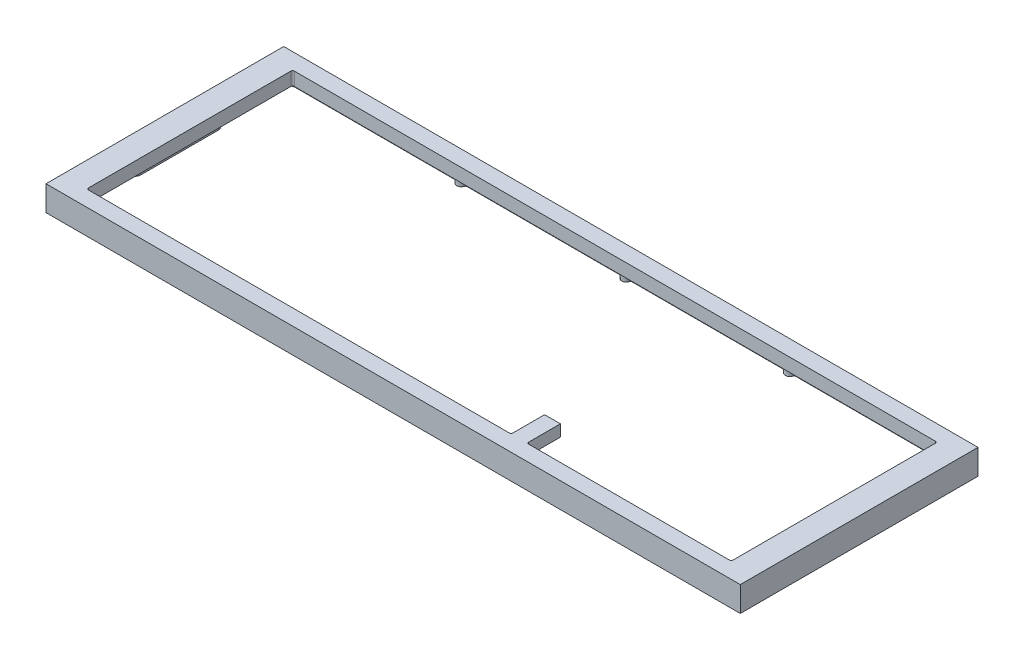
SolidWorks part; units mm, degrees
ref_plane "Front Plane" through (0, 0, 0) normal (0, 0, 1) x (1, 0, 0)
ref_plane "Top Plane" through (0, 0, 0) normal (0, 1, 0) x (1, 0, 0)
ref_plane "Right Plane" through (0, 0, 0) normal (1, 0, 0) x (0, 0, -1)
sketch "Sketch1" plane through (0, 0, 0) normal (0, 1, 0) x (1, 0, 0)
  line L1 (0, 0) -> (390.8, 0)
  line L2 (0, 0) -> (0, -133.8)
  line L3 (0, -133.8) -> (390.8, -133.8)
  line L4 (390.8, 0) -> (390.8, -133.8)
  dimension "D1" = 390.8
  dimension "D2" = 133.8
extrude "Boss-Extrude1" add sketch "Sketch1" along normal blind 14.1
sketch "Sketch2" plane through (0, 14.1, 0) normal (0, 1, 0) x (1, 0, 0)
  line L0 (390.8, 0) -> (0, 0) construction
  line L1 (14, -9) -> (376.8, -9)
  line L2 (14, -9) -> (14, -124.9)
  line L3 (14, -124.9) -> (376.8, -124.9)
  line L4 (376.8, -9) -> (376.8, -124.9)
  line L5 (0, -133.8) -> (390.8, -133.8) construction
  line L6 (0, 0) -> (0, -133.8) construction
  line L7 (390.8, -133.8) -> (390.8, 0) construction
  line L8 (390.8, -133.8) -> (390.8, 0) construction
  line L9 (261.8, -124.9) -> (252.9, -124.9)
  line L10 (261.8, -124.9) -> (261.8, -106.05)
  line L11 (261.8, -106.05) -> (252.9, -106.05)
  line L12 (252.9, -124.9) -> (252.9, -106.05)
  line L13 (0, -133.8) -> (390.8, -133.8) construction
  dimension "D1" = 9
  dimension "D2" = 8.9
  dimension "D3" = 14
  dimension "D4" = 14
  dimension "D5" = 129
  dimension "D6" = 137.9
  dimension "D7" = 27.75
extrude "Cut-Extrude1" cut sketch "Sketch2" against normal through all contours L3 L12 L11 L10 L4 L1 L2 region at (195.1518, 14.1, 66.7556)
sketch "Sketch3" plane through (0, 0, 0) normal (0, -1, 0) x (1, 0, 0)
  line L0 (390.8, 0) -> (0, 0) construction
  line L1 (385.5, 2.6) -> (5.3, 2.6)
  line L2 (385.5, 2.6) -> (385.5, 131.2)
  line L3 (385.5, 131.2) -> (5.3, 131.2)
  line L4 (5.3, 2.6) -> (5.3, 131.2)
  line L5 (390.8, 133.8) -> (390.8, 0) construction
  point P4 (195.4, 2.6)
  point P7 (195.4, 0)
  point P8 (385.5, 66.9)
  point P11 (390.8, 66.9)
  dimension "D1" = 380.2
  dimension "D2" = 128.6
extrude "Cut-Extrude2" cut sketch "Sketch3" against normal blind 6.6 contours L2 L1 L4 L3
sketch "Sketch5" plane through (0, 6.6, 0) normal (0, -1, 0) x (1, 0, 0)
  line L0 (290, 128.2) -> (285, 128.2)
  line L1 (290, 128.2) -> (290, 131.2)
  line L2 (290, 131.2) -> (285, 131.2)
  line L3 (285, 128.2) -> (285, 131.2)
  line L4 (105, 128.2) -> (100, 128.2)
  line L5 (105, 128.2) -> (105, 131.2)
  line L6 (105, 131.2) -> (100, 131.2)
  line L7 (100, 128.2) -> (100, 131.2)
  line L8 (8.3, 45) -> (8.3, 88.8)
  line L9 (382.5, 45) -> (382.5, 88.8)
  line L10 (0, 133.8) -> (390.8, 133.8) construction
  line L11 (5.3, 2.6) -> (5.3, 131.2) construction
  line L12 (390.8, 0) -> (0, 0) construction
  line L13 (385.5, 2.6) -> (385.5, 131.2) construction
  line L15 (385.5, 131.2) -> (5.3, 131.2) construction
  line L16 (385.5, 131.2) -> (5.3, 131.2) construction
  line L17 (385.5, 2.6) -> (5.3, 2.6) construction
  line L18 (5.3, 2.6) -> (5.3, 131.2) construction
  circle A0 centre (102.5, 128.2) radius 2.5
  circle A1 centre (287.5, 128.2) radius 2.5
  circle A2 centre (102.5, 2.6) radius 2.5
  circle A3 centre (195.4, 2.6) radius 2.5
  circle A4 centre (287.5, 2.6) radius 2.5
  circle A5 centre (385.5, 45) radius 3
  circle A6 centre (385.5, 88.8) radius 3
  circle A7 centre (5.3, 45) radius 3
  circle A8 centre (5.3, 88.8) radius 3
  point P26 (0, 0)
  point P35 (0, 0)
  point P38 (0, 0)
  line M9 (5.3, 131.2) -> (5.3, 2.6)
  line M10 (5.3, 2.6) -> (385.5, 2.6)
  line M11 (385.5, 2.6) -> (385.5, 131.2)
  dimension "D1" = 5
  dimension "D5" = 6
  dimension "D2" = 185
  dimension "D3" = 92.9
  dimension "D4" = 185
  dimension "D6" = 45
  dimension "D7" = 97.2
  dimension "D8" = 3
  dimension "D9" = 97.2
  dimension "D10" = 45
  dimension "D11" = 45
extrude "Boss-Extrude2" add sketch "Sketch5" along normal up to surface (6.6 mm away) contours A6 L9 A5 M11 | A5 M11 | A6 M11 | A4 M10 | A3 M10 | A2 M10 | A7 M9 | A8 A7 L8 M9 | A8 M9 | A0 | L7 L6 L5 L4 | L3 L2 L1 L0 | A1 region at (6.8273, 6.6, 66.9) region at (6.5732, 6.6, 45) region at (384.2268, 6.6, 45) region at (287.5, 6.6, 3.661) region at (195.4, 6.6, 3.661) region at (102.5, 6.6, 3.661) region at (6.5732, 6.6, 88.8) region at (383.9727, 6.6, 66.9) region at (384.2268, 6.6, 88.8) up to face at (195.4, 0, 66.9)
sketch "Sketch6" plane through (0, 6.6, 0) normal (0, -1, 0) x (-1, 0, 0)
  line L0 (-195.4, 0) -> (-195.4, -133.8) construction
  line L1 (-390.8, 0) -> (0, 0) construction
  line L2 (0, -133.8) -> (-390.8, -133.8) construction
  line L3 (-390.8, -66.9) -> (0, -66.9) construction
  line L4 (-390.8, -133.8) -> (-390.8, 0) construction
  line L5 (0, 0) -> (0, -133.8) construction
  point P12 (-382.9, -22.7)
  point P13 (-382.9, -111)
  point P14 (-325.4, -129)
  point P15 (-195.4, -129)
  point P16 (0, 0)
  point P17 (0, 0)
  point P18 (-65.4, -129)
  point P19 (-7.9, -111)
  point P20 (-7.9, -22.7)
  dimension "D1" = 22.8
  dimension "D2" = 22.7
  dimension "D3" = 7.9
  dimension "D4" = 65.4
  dimension "D5" = 4.8
sketch "Sketch7" plane through (0, 0, 0) normal (0, -1, 0) x (1, 0, 0)
  arc A0 (382.5, 45) -> (385.5, 42) centre (385.5, 45) ccw construction
  arc A1 (385.5, 91.8) -> (382.5, 88.8) centre (385.5, 88.8) ccw construction
  arc A2 (290, 2.6) -> (285, 2.6) centre (287.5, 2.6) ccw construction
  arc A3 (197.9, 2.6) -> (192.9, 2.6) centre (195.4, 2.6) ccw construction
  arc A4 (105, 2.6) -> (100, 2.6) centre (102.5, 2.6) ccw construction
  arc A5 (5.3, 42) -> (8.3, 45) centre (5.3, 45) ccw construction
  arc A6 (8.3, 88.8) -> (5.3, 91.8) centre (5.3, 88.8) ccw construction
  arc A7 (100, 128.2) -> (105, 128.2) centre (102.5, 128.2) ccw construction
  arc A8 (285, 128.2) -> (290, 128.2) centre (287.5, 128.2) ccw construction
  point P0 (385.5, 45)
  point P1 (385.5, 88.8)
  point P2 (287.5, 128.2)
  point P3 (102.5, 128.2)
  point P4 (5.3, 88.8)
  point P5 (5.3, 45)
  point P6 (102.5, 2.6)
  point P7 (195.4, 2.6)
  point P8 (287.5, 2.6)
  point P10 (0, 0)
  point P15 (0, 0)
  point P19 (0, 0)
  point P23 (0, 0)
  point P27 (0, 0)
  point P31 (0, 0)
  point P32 (0, 0)
  point P36 (0, 0)
  point P40 (0, 0)
  point P44 (0, 0)
sketch "Sketch8" plane through (0, 6.6, 0) normal (0, -1, 0) x (1, 0, 0)
  line L1 (261.8, 106.05) -> (252.9, 106.05)
  line L2 (261.8, 106.05) -> (261.8, 124.9)
  line L3 (261.8, 124.9) -> (252.9, 124.9)
  line L4 (252.9, 106.05) -> (252.9, 124.9)
extrude "Cut-Extrude3" cut sketch "Sketch8" against normal blind 1
hole_wizard "M2x0.4 Tapped Hole1" positions "3DSketch2" profile "Sketch10" tap size "M2x0.4" standard "ANSI Metric"
sketch3d "3DSketch2"
  point P0 (385.5, 0, 45)
  point P3 (385.5, 0, 88.8)
  point P6 (287.5, 0, 128.2)
  point P9 (102.5, 0, 128.2)
  point P12 (5.3, 0, 88.8)
  point P15 (5.3, 0, 45)
  point P18 (102.5, 0, 2.6)
  point P21 (287.5, 0, 2.6)
  point P24 (195.4, 0, 2.6)
sketch "Sketch10" plane through (385.5, 0, 45) normal (1, 0, 0) x (0, 0, -1)
  line L0 (0, 0) -> (0, 11.4807)
  line L1 (0, 11.4807) -> (0.8, 11)
  line L2 (0.8, 11) -> (0.8, 0)
  line L5 (0.8, 0) -> (0, 0)
  line L10 (0, 11.4807) -> (-0.8, 11) construction
  line L11 (0, -6.35) -> (0, 107.95) construction
  dimension "Tap Drill Dia." = 1.6
  dimension "Tap Drill Depth" = 11
  dimension "Drill Angle" = 118
cosmetic thread "Hole Thread1" parameters "D1"=4, "D2"=2
cosmetic thread "Hole Thread2" parameters "D1"=4, "D2"=2
cosmetic thread "Hole Thread3" parameters "D1"=4, "D2"=2
cosmetic thread "Hole Thread4" parameters "D1"=4, "D2"=2
cosmetic thread "Hole Thread5" parameters "D1"=4, "D2"=2
cosmetic thread "Hole Thread6" parameters "D1"=4, "D2"=2
cosmetic thread "Hole Thread7" parameters "D1"=4, "D2"=2
cosmetic thread "Hole Thread8" parameters "D1"=4, "D2"=2
cosmetic thread "Hole Thread9" parameters "D1"=4, "D2"=2
hole_wizard "M2x0.4 Tapped Hole2" positions "3DSketch3" profile "Sketch11" tap size "M2x0.4" standard "ANSI Metric"
sketch3d "3DSketch3"
  point P0 (382.9, 6.6, 22.7)
  point P3 (382.9, 6.6, 111)
  point P6 (325.4, 6.6, 129)
  point P9 (195.4, 6.6, 129)
  point P12 (65.4, 6.6, 129)
  point P15 (7.9, 6.6, 22.7)
  point P18 (7.9, 6.6, 111)
sketch "Sketch11" plane through (382.9, 6.6, 22.7) normal (1, 0, 0) x (0, 0, -1)
  line L0 (0, 0) -> (0, 4.9807)
  line L1 (0, 4.9807) -> (0.8, 4.5)
  line L2 (0.8, 4.5) -> (0.8, 0)
  line L5 (0.8, 0) -> (0, 0)
  line L10 (0, 4.9807) -> (-0.8, 4.5) construction
  line L11 (0, -6.35) -> (0, 107.95) construction
  dimension "Tap Drill Dia." = 1.6
  dimension "Tap Drill Depth" = 4.5
  dimension "Drill Angle" = 118
cosmetic thread "Hole Thread10" parameters "D1"=4, "D2"=2
cosmetic thread "Hole Thread11" parameters "D1"=4, "D2"=2
cosmetic thread "Hole Thread12" parameters "D1"=4, "D2"=2
cosmetic thread "Hole Thread13" parameters "D1"=4, "D2"=2
cosmetic thread "Hole Thread14" parameters "D1"=4, "D2"=2
cosmetic thread "Hole Thread15" parameters "D1"=4, "D2"=2
cosmetic thread "Hole Thread16" parameters "D1"=4, "D2"=2
fillet "Fillet1" radius 4 12 edges at (385.5, 3.3, 42) (385.5, 3.3, 2.6) (5.3, 3.3, 2.6) (5.3, 3.3, 42) (5.3, 3.3, 91.8) (5.3, 3.3, 131.2) (100, 3.3, 131.2) (105, 3.3, 131.2) (290, 3.3, 131.2) (285, 3.3, 131.2) (385.5, 3.3, 131.2) (385.5, 3.3, 91.8)
fillet "Fillet2" radius 1 12 edges at (376.8, 10.35, 9) (376.8, 10.35, 124.9) (14, 10.35, 124.9) (14, 10.35, 9) (105, 3.3, 2.6) (100, 3.3, 2.6) (197.9, 3.3, 2.6) (192.9, 3.3, 2.6) (285, 3.3, 2.6) (290, 3.3, 2.6) (261.8, 10.85, 124.9) (252.9, 10.85, 124.9)
sketch "Sketch12" plane through (0, 0, 0) normal (0, -1, 0) x (1, 0, 0)
  line L0 (390.8, 0) -> (0, 0) construction
  line L1 (58.0819, 0) -> (42.8819, 0)
  line L2 (58.0819, 0) -> (58.0819, 2)
  line L3 (58.0819, 2) -> (42.8819, 2)
  line L4 (42.8819, 0) -> (42.8819, 2)
  dimension "D1" = 2
  dimension "D2" = 15.2
extrude "Cut-Extrude4" cut sketch "Sketch12" against normal blind 2
fillet "Fillet3" radius 4 2 edges at (42.8819, 1, 2) (58.0819, 1, 2)
